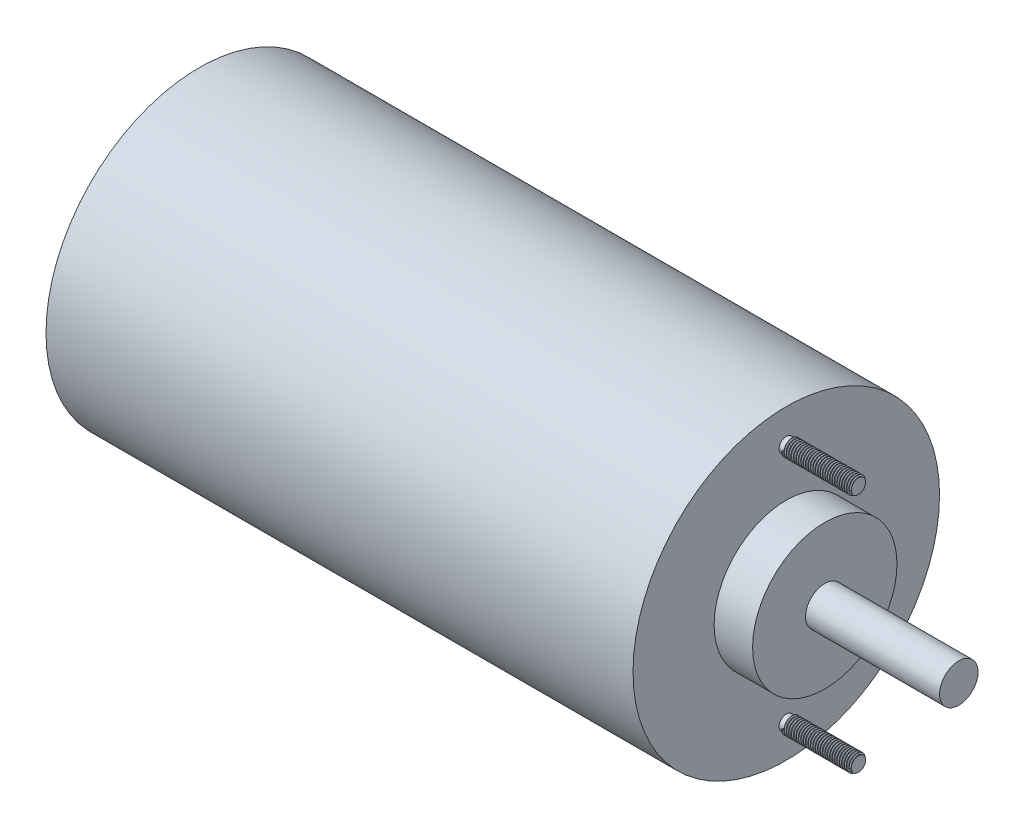
SolidWorks part; units mm, degrees
ref_plane "Front Plane" through (0, 0, 0) normal (0, 0, 1) x (1, 0, 0)
ref_plane "Top Plane" through (0, 0, 0) normal (0, 1, 0) x (1, 0, 0)
ref_plane "Right Plane" through (0, 0, 0) normal (1, 0, 0) x (0, 0, -1)
sketch "Sketch1" plane through (0, 0, 0) normal (0, 0, 1) x (1, 0, 0)
  line L0 (-50, 0) -> (50, 0) construction
  line L1 (122, 4) -> (122, 31.85)
  line L2 (122, 31.85) -> (0, 31.85)
  line L3 (0, 31.85) -> (0, 0)
  line L5 (122, 4) -> (157.85, 4)
  line L6 (157.85, 4) -> (157.85, 0)
  line L7 (0, 0) -> (157.85, 0)
  point P4 (0, 0)
  dimension "D1" = 31.85
  dimension "D2" = 122
  dimension "D3" = 4
  dimension "D4" = 35.85
revolve "Revolve2" add sketch "Sketch1" angle 360 about L0
sketch "Sketch2" plane through (122, 0, 0) normal (1, 0, 0) x (0, 0, -1)
  circle A0 centre (0, 0) radius 15
  dimension "D1" = 30
extrude "Boss-Extrude1" add sketch "Sketch2" along normal blind 8
sketch "Sketch3" plane through (122, 0, 0) normal (1, 0, 0) x (0, 0, -1)
  line L0 (0, 25) -> (0, -25) construction
  circle A0 centre (0, 25) radius 1.5
  circle A1 centre (0, -25) radius 1.5
  point P6 (0, 0)
  dimension "D2" = 3
  dimension "D3" = 3
  dimension "D1" = 50
extrude "Boss-Extrude2" add sketch "Sketch3" along normal blind 15
thread "Thread1" pitch 0.5 method extrude profile "Thread Profile1" start angle 0, offset 0, length 14, pitch 0.5, diameter 3
ref_plane "Plane1" through (137, 25, 1.5) normal (0, -1, 0) x (0, 0, 1)
sketch "Thread Profile1" plane through (137, 25, 1.5) normal (0, -1, 0) x (0, 0, 1)
  line L0 (0, 0) -> (0, 0.5) construction
  line L1 (0, 0) -> (0.2706, 0.1562)
  line L2 (0.2706, 0.1562) -> (0.2706, 0.2187)
  line L3 (0.2706, 0.2187) -> (0, 0.375)
  line L4 (0.2706, 0.1875) -> (0, 0.1875) construction
  line L11 (0, 0) -> (0, 0.375)
  point P2 (0, 0)
  dimension "Pitch" = 0.5
  dimension "Profile_Angle" = 60
  dimension "Profile_Land" = 0.0625
  dimension "Profile_Height" = 0.2706
thread "Thread2" pitch 0.5 method extrude profile "Thread Profile2" start angle 0, offset 0, length 14, pitch 0.5, diameter 3
ref_plane "Plane2" through (137, -25, 1.5) normal (0, -1, 0) x (0, 0, 1)
sketch "Thread Profile2" plane through (137, -25, 1.5) normal (0, -1, 0) x (0, 0, 1)
  line L0 (0, 0) -> (0, 0.5) construction
  line L1 (0, 0) -> (0.2706, 0.1562)
  line L2 (0.2706, 0.1562) -> (0.2706, 0.2187)
  line L3 (0.2706, 0.2187) -> (0, 0.375)
  line L4 (0.2706, 0.1875) -> (0, 0.1875) construction
  line L11 (0, 0) -> (0, 0.375)
  point P2 (0, 0)
  dimension "Pitch" = 0.5
  dimension "Profile_Angle" = 60
  dimension "Profile_Land" = 0.0625
  dimension "Profile_Height" = 0.2706
